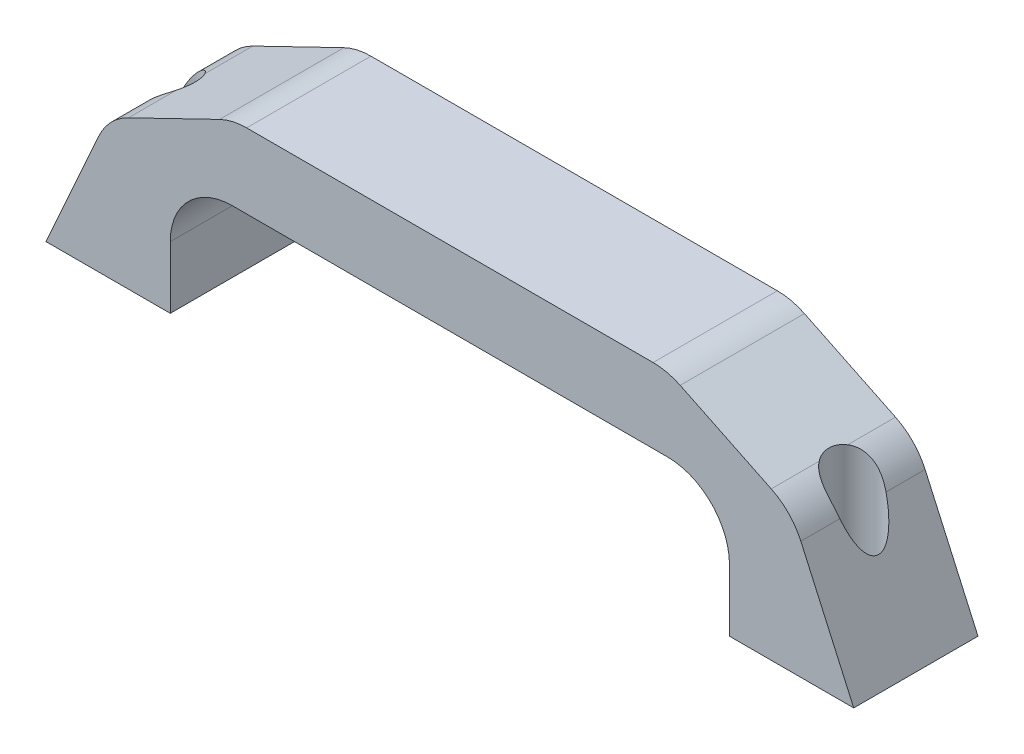
SolidWorks part; units mm, degrees
ref_plane "Plano frontal" through (0, 0, 0) normal (0, 0, 1) x (1, 0, 0)
ref_plane "Plano superior" through (0, 0, 0) normal (0, 1, 0) x (1, 0, 0)
ref_plane "Plano direito" through (0, 0, 0) normal (1, 0, 0) x (0, 0, -1)
sketch "Esboço1" plane through (0, 0, 0) normal (0, 0, 1) x (1, 0, 0)
  line L1 (-65, 16) -> (65, 16)
  line L2 (-65, 16) -> (-65, -16)
  line L3 (-65, -16) -> (65, -16)
  line L4 (65, 16) -> (65, -16)
  line L5 (-65, 16) -> (65, -16) construction
  line L6 (-65, -16) -> (65, 16) construction
  point P0 (0, 0)
  dimension "D1" = 130
  dimension "D2" = 32
extrude "Ressalto-extrusão1" add sketch "Esboço1" along normal blind 10 and the other way blind 10
sketch "Esboço2" plane through (0, 0, 10) normal (0, 0, 1) x (1, 0, 0)
  line L0 (35, 16) -> (55, 6.308)
  line L1 (65, 16) -> (-65, 16) construction
  line L2 (-65, -16) -> (-65, 16)
  line L3 (0, 16) -> (0, -16) construction
  line L4 (-65, -16) -> (65, -16) construction
  line L5 (-55, 6.308) -> (-65, -16)
  line L6 (55, 6.308) -> (65, -16)
  line L7 (-45, 4) -> (45, 4)
  line L8 (-45, 4) -> (-45, -16)
  line L9 (-45, -16) -> (45, -16)
  line L10 (45, 4) -> (45, -16)
  line L11 (-45, 4) -> (45, -16) construction
  line L12 (-45, -16) -> (45, 4) construction
  line L13 (65, -16) -> (65, 16)
  line L14 (65, 16) -> (35, 16)
  line L15 (-65, 16) -> (-35, 16)
  line L16 (-35, 16) -> (-55, 6.308)
  point P10 (0, -6)
  dimension "D1" = 20
  dimension "D2" = 90
  dimension "D3" = 30
  dimension "D4" = 140
  dimension "D5" = 10
extrude "Corte-extrusão1" cut sketch "Esboço2" against normal through all
fillet "Filete1" radius 10 6 edges at (45, 4, 0) (-45, 4, 0) (55, 6.308, 0) (35, 16, 0) (-35, 16, 0) (-55, 6.308, 0)
sketch "Esboço4" plane through (0, 16, 0) normal (0, 1, 0) x (1, 0, 0)
  line L0 (-51.7246, 10) -> (-37.0656, 10) construction
  line L1 (0, 10) -> (0, -10) construction
  line L2 (32.7047, 10) -> (-32.7047, 10) construction
  line L3 (32.7047, -10) -> (-32.7047, -10) construction
  circle A0 centre (-55, 0) radius 4
  circle A1 centre (55, 0) radius 4
  dimension "D1" = 8
  dimension "D2" = 55
  dimension "D3" = 10
extrude "Corte-extrusão2" cut sketch "Esboço4" against normal blind 29.5
sketch "Esboço5" plane through (0, 16, 0) normal (0, 1, 0) x (1, 0, 0)
  line L0 (0, 10) -> (0, -10) construction
  line L1 (32.7047, 10) -> (-32.7047, 10) construction
  line L2 (32.7047, -10) -> (-32.7047, -10) construction
  circle A0 centre (-55, 0) radius 2.25
  circle A1 centre (55, 0) radius 2.25
  dimension "D1" = 4.5
extrude "Corte-extrusão3" cut sketch "Esboço5" against normal through all
